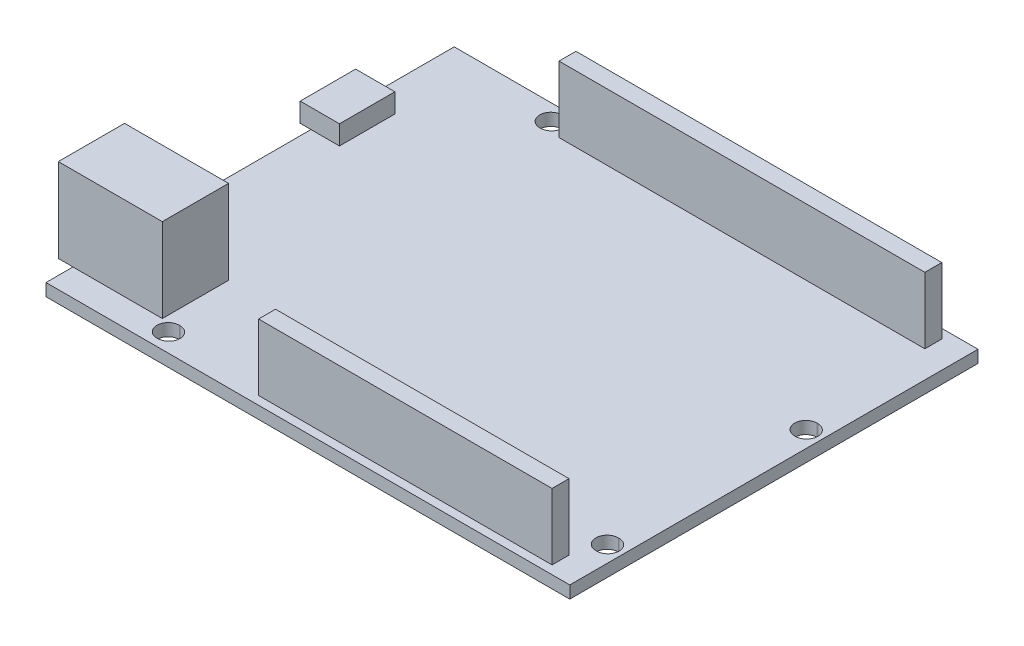
SolidWorks part; units mm, degrees
ref_plane "Front Plane" through (0, 0, 0) normal (0, 0, 1) x (1, 0, 0)
ref_plane "Top Plane" through (0, 0, 0) normal (0, 1, 0) x (1, 0, 0)
ref_plane "Right Plane" through (0, 0, 0) normal (1, 0, 0) x (0, 0, -1)
sketch "Sketch1" plane through (0, 0, 0) normal (0, 1, 0) x (1, 0, 0)
  line L1 (0, 0) -> (68, 0)
  line L2 (0, 0) -> (0, 53)
  line L3 (0, 53) -> (68, 53)
  line L4 (68, 0) -> (68, 53)
  dimension "D1" = 68
  dimension "D2" = 53
extrude "Boss-Extrude1" add sketch "Sketch1" along normal blind 1.6
hole_wizard "M2.5 Clearance Slot1" positions "Sketch2" profile "Sketch3" size "M2.5" standard "ANSI Metric" slot yes end condition through all
sketch "Sketch2" plane through (0, 1.6, 0) normal (0, 1, 0) x (1, 0, 0)
  line L0 (0, 53) -> (0, 0) construction
  line L1 (0, 0) -> (68, 0) construction
  line L2 (68, 0) -> (68, 53) construction
  line L3 (68, 53) -> (0, 53) construction
  line L4 (12, 2.4) -> (15, 2.4) construction
  point P0 (13.5, 2.4)
  point P2 (65.9, 7)
  point P4 (65.9, 32.8)
  point P6 (14.7, 50.9)
  dimension "D1" = 13.5
  dimension "D2" = 2.4
  dimension "D3" = 7
  dimension "D4" = 2.1
  dimension "D5" = 2.1
  dimension "D6" = 32.8
  dimension "D7" = 2.1
  dimension "D8" = 14.7
sketch "Sketch3" plane through (13.5, 1.6, -2.4) normal (1, 0, 0) x (0, 0, 1)
  line L0 (0, 0) -> (0, 1.6)
  line L1 (0, 1.6) -> (1.45, 1.6)
  line L2 (1.45, 1.6) -> (1.45, 0)
  line L5 (1.45, 0) -> (0, 0)
  line L11 (0, -6.35) -> (0, 107.95) construction
  dimension "Thru Hole Dia." = 2.9
  dimension "Thru Hole Depth" = 1.6
sketch "Sketch4" plane through (0, 1.6, 0) normal (0, 1, 0) x (1, 0, 0)
  line L0 (0, 53) -> (0, 0) construction
  line L1 (17, 49.6) -> (64.5, 49.6)
  line L2 (17, 49.6) -> (17, 51.8)
  line L3 (17, 51.8) -> (64.5, 51.8)
  line L4 (64.5, 49.6) -> (64.5, 51.8)
  line L5 (64.6, 1.1) -> (26.5, 1.1)
  line L6 (64.6, 1.1) -> (64.6, 3.3)
  line L7 (64.6, 3.3) -> (26.5, 3.3)
  line L8 (26.5, 1.1) -> (26.5, 3.3)
  line L9 (0, 0) -> (68, 0) construction
  line L10 (68, 53) -> (0, 53) construction
  dimension "D1" = 2.2
  dimension "D2" = 2.2
  dimension "D3" = 38.1
  dimension "D4" = 47.5
  dimension "D5" = 26.5
  dimension "D6" = 17
  dimension "D7" = 1.1
  dimension "D8" = 1.2
extrude "Boss-Extrude2" add sketch "Sketch4" along normal blind 8.6
sketch "Sketch5" plane through (0, 1.6, 0) normal (0, 1, 0) x (1, 0, 0)
  line L0 (0, 53) -> (0, 0) construction
  line L1 (11.6, 3.5) -> (-1.9, 3.5)
  line L2 (11.6, 3.5) -> (11.6, 12.1)
  line L3 (11.6, 12.1) -> (-1.9, 12.1)
  line L4 (-1.9, 3.5) -> (-1.9, 12.1)
  line L5 (0, 0) -> (68, 0) construction
  dimension "D1" = 8.6
  dimension "D2" = 13.5
  dimension "D3" = 1.9
  dimension "D4" = 3.5
extrude "Boss-Extrude3" add sketch "Sketch5" along normal blind 10.9
sketch "Sketch6" plane through (0, 1.6, 0) normal (0, 1, 0) x (1, 0, 0)
  line L0 (0, 53) -> (0, 12.1) construction
  line L1 (3.7, 34.4) -> (-1.4, 34.4)
  line L2 (3.7, 34.4) -> (3.7, 41.6)
  line L3 (3.7, 41.6) -> (-1.4, 41.6)
  line L4 (-1.4, 34.4) -> (-1.4, 41.6)
  line L5 (68, 53) -> (0, 53) construction
  dimension "D1" = 7.2
  dimension "D2" = 5.1
  dimension "D3" = 1.4
  dimension "D4" = 11.4
extrude "Boss-Extrude4" add sketch "Sketch6" along normal blind 2.5
